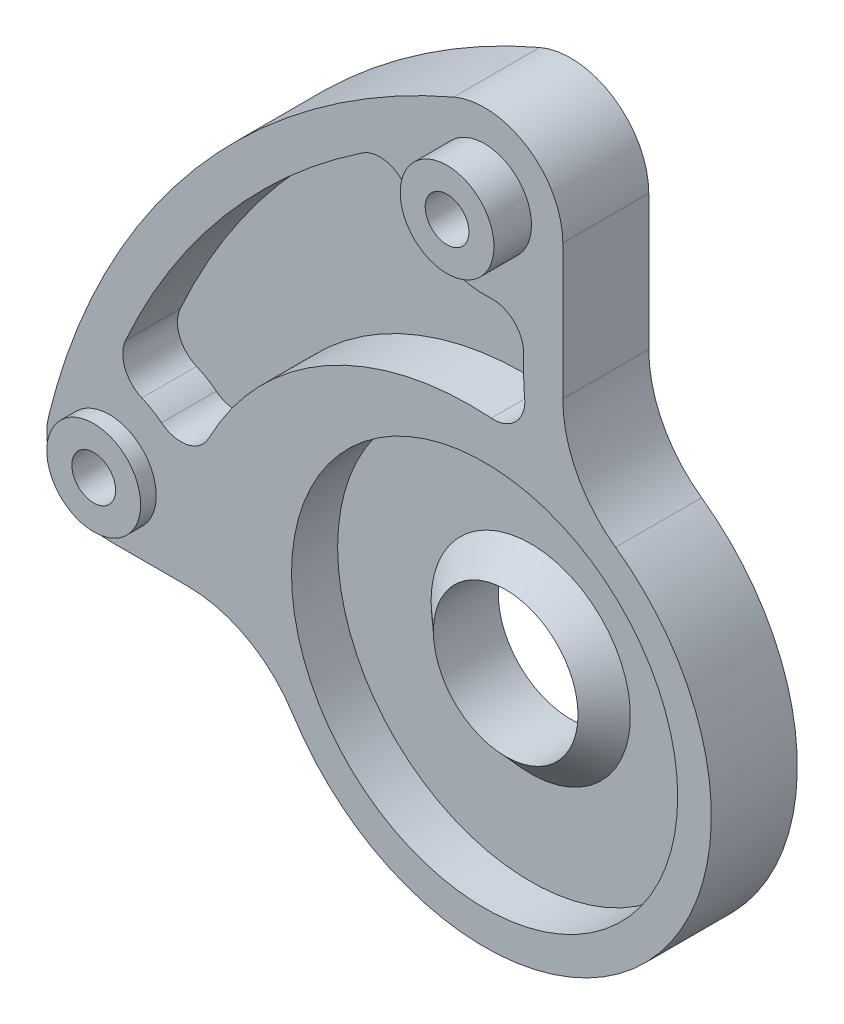
SolidWorks part; units mm, degrees
ref_plane "Front Plane" through (0, 0, 0) normal (0, 0, 1) x (1, 0, 0)
ref_plane "Top Plane" through (0, 0, 0) normal (0, 1, 0) x (1, 0, 0)
ref_plane "Right Plane" through (0, 0, 0) normal (1, 0, 0) x (0, 0, -1)
ref_plane "Plane1" through (0, 0, 5.5) normal (0, 0, 1) x (1, 0, 0)
sketch "Sketch1" plane through (0, 0, 5.5) normal (0, 0, 1) x (1, 0, 0)
  line L0 (5, 18.3644) -> (5, 27)
  line L1 (-24, -4) -> (-19.0329, -4)
  arc A0 (8.3778, 11.8348) -> (5, 18.3644) centre (13, 18.3644) cw
  arc A1 (5, 27) -> (-1.9784, 31.5919) centre (0, 27) ccw
  arc A2 (-1.9784, 31.5919) -> (-27.8856, 0.9498) centre (15.8274, -9.7355) ccw
  arc A3 (-27.8856, 0.9498) -> (-24, -4) centre (-24, 0) ccw
  arc A4 (-19.0329, -4) -> (-12.2656, -7.7333) centre (-19.0329, -12) cw
  arc A5 (-12.2656, -7.7333) -> (8.3778, 11.8348) centre (0, 0) ccw
extrude "Boss-Extrude1" add sketch "Sketch1" against normal blind 5.5
sketch "Sketch2" plane through (0, 0, 5.5) normal (0, 0, 1) x (1, 0, 0)
  circle A0 centre (0, 27) radius 3
  dimension "D1" = 6
extrude "Boss-Extrude2" add sketch "Sketch2" along normal blind 2.4
sketch "Sketch3" plane through (0, 0, 5.5) normal (0, 0, 1) x (1, 0, 0)
  circle A0 centre (-24, 0) radius 3
  dimension "D1" = 6
extrude "Boss-Extrude3" add sketch "Sketch3" along normal blind 1
sketch "Sketch4" plane through (0, 0, 0) normal (0, 0, -1) x (-1, 0, 0)
  circle A0 centre (0, 0) radius 4.625
  dimension "D1" = 9.25
extrude "Cut-Extrude1" cut sketch "Sketch4" against normal through all
sketch "Sketch5" plane through (0, 0, 7.9) normal (0, 0, 1) x (1, 0, 0)
  circle A0 centre (0, 27) radius 1.4
  circle A1 centre (-24, 0) radius 1.4
  dimension "D1" = 2.8
extrude "Cut-Extrude2" cut sketch "Sketch5" against normal through all
sketch "Sketch7" plane through (0, 0, 5.5) normal (0, 0, 1) x (1, 0, 0)
  circle A0 centre (0, 0) radius 12.35
  circle A1 centre (0, 0) radius 12.1 construction
  dimension "D1" = 0.25
  dimension "D2" = 24.2
extrude "Cut-Extrude4" cut sketch "Sketch7" against normal blind 2.95
sketch "Sketch8" plane through (0, 0, 5.5) normal (0, 0, 1) x (1, 0, 0)
  line L0 (2.5, 18.3644) -> (2.5, 19.6403)
  arc A0 (0.3644, 21.6357) -> (-4.8853, 24.7546) centre (0, 27) cw
  arc A1 (-4.8853, 24.7546) -> (-7.8152, 25.5814) centre (-6.7026, 23.9194) ccw
  arc A2 (-7.8152, 25.5814) -> (-22.9686, 7.6175) centre (15.8274, -9.7355) ccw
  arc A3 (-22.9686, 7.6175) -> (-21.9175, 4.957) centre (-21.1429, 6.8009) ccw
  arc A4 (-21.9175, 4.957) -> (-20.6588, 4.2124) centre (-24, 0) cw
  arc A5 (-20.6588, 4.2124) -> (-17.6384, 4.8627) centre (-19.4159, 5.7794) ccw
  arc A6 (-17.6384, 4.8627) -> (0.4318, 15.0138) centre (-0.9047, -3.7663) cw
  arc A7 (0.4318, 15.0138) -> (2.5619, 17.2256) centre (0.5737, 17.0087) ccw
  arc A8 (2.5619, 17.2256) -> (2.5, 18.3644) centre (13, 18.3644) cw
  arc A9 (2.5, 19.6403) -> (0.3644, 21.6357) centre (0.5, 19.6403) ccw
extrude "Cut-Extrude5" cut sketch "Sketch8" against normal blind 3.5
sketch "Sketch9" plane through (0, 0, 2.55) normal (0, 0, 1) x (1, 0, 0)
  circle A0 centre (0, 0) radius 4.625 construction
  circle A1 centre (0, 0) radius 4.625
  circle A3 centre (0, 0) radius 6.375
  dimension "D2" = 1.75
extrude "Boss-Extrude4" add sketch "Sketch9" along normal blind 1.6
chamfer "Chamfer1" distance 1.6 distance2 1.75 1 edges at (6.375, 0, 4.15) first distance on face at (6.375, 0, 4.15)
